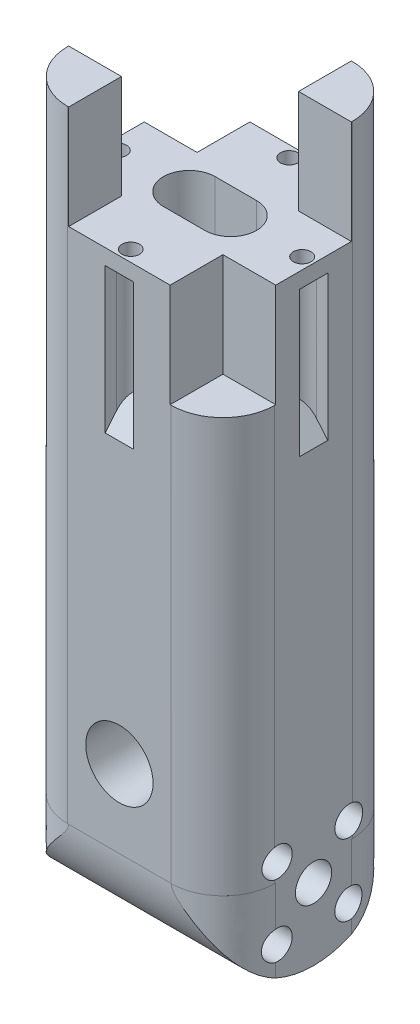
SolidWorks part; units mm, degrees
ref_plane "Plan de face" through (0, 0, 0) normal (0, 0, 1) x (1, 0, 0)
ref_plane "Plan de dessus" through (0, 0, 0) normal (0, 1, 0) x (1, 0, 0)
ref_plane "Plan de droite" through (0, 0, 0) normal (1, 0, 0) x (0, 0, -1)
sketch "Esquisse3" plane through (0, 0, 0) normal (0, 1, 0) x (1, 0, 0)
  line L1 (-20, -17.5) -> (20, -17.5)
  line L2 (-20, -17.5) -> (-20, 17.5)
  line L3 (-20, 17.5) -> (20, 17.5)
  line L4 (20, -17.5) -> (20, 17.5)
  line L5 (-20, -17.5) -> (20, 17.5) construction
  line L6 (-20, 17.5) -> (20, -17.5) construction
  point P0 (0, 0)
  dimension "D1" = 40
  dimension "D2" = 35
extrude "Boss.-Extru.2" add sketch "Esquisse3" along normal blind 120
fillet "Congé1" radius 10 4 edges at (-20, 60, -17.5) (-20, 60, 17.5) (20, 60, -17.5) (20, 60, 17.5)
sketch "Esquisse4" plane through (0, 120, 0) normal (0, 1, 0) x (1, 0, 0)
  line L10 (-20, 17.5) -> (9.8, 17.5)
  line L11 (9.8, 17.5) -> (9.8, 7.3)
  line L12 (9.8, 7.3) -> (20, 7.3)
  line L13 (20, 7.3) -> (20, -17.5)
  line L14 (20, -17.5) -> (-9.8, -17.5)
  line L15 (-9.8, -17.5) -> (-9.8, -7.3)
  line L16 (-9.8, -7.3) -> (-20, -7.3)
  line L17 (-20, -7.3) -> (-20, 17.5)
  line L19 (20, -7.5) -> (20, 7.5) construction
  line L20 (10, 17.5) -> (-10, 17.5) construction
  line L21 (-20, 7.5) -> (-20, -7.5) construction
  line L22 (-10, -17.5) -> (10, -17.5) construction
  arc A0 (-20, -7.5) -> (-10, -17.5) centre (-10, -7.5) ccw construction
  arc A1 (20, 7.5) -> (10, 17.5) centre (10, 7.5) ccw construction
  dimension "D4" = 0.2
  dimension "D1" = 0.2
  dimension "D2" = 0.2
  dimension "D3" = 0.2
extrude "Enlèv. mat.-Extru.1" cut sketch "Esquisse4" against normal blind 20
sketch "Esquisse5" plane through (0, 100, 0) normal (0, 1, 0) x (1, 0, 0)
  line L0 (-20, 7.5) -> (-20, -7.3) construction
  line L9 (-20, 17.5) -> (-9.8, 17.5)
  line L10 (-20, 17.5) -> (-20, 7.3)
  line L11 (-20, 7.3) -> (-9.8, 7.3)
  line L12 (-9.8, 17.5) -> (-9.8, 7.3)
  line L13 (20, -17.5) -> (9.8, -17.5)
  line L14 (20, -17.5) -> (20, -7.3)
  line L15 (20, -7.3) -> (9.8, -7.3)
  line L16 (9.8, -17.5) -> (9.8, -7.3)
  line L17 (9.8, 17.5) -> (-10, 17.5) construction
  line L18 (20, -7.5) -> (20, 7.3) construction
  line L19 (-9.8, -17.5) -> (10, -17.5) construction
  arc A0 (-10, 17.5) -> (-20, 7.5) centre (-10, 7.5) ccw construction
  arc A1 (10, -17.5) -> (20, -7.5) centre (10, -7.5) ccw construction
  dimension "D2" = 0.2
  dimension "D1" = 0.2
  dimension "D3" = 0.2
  dimension "D4" = 0.2
extrude "Enlèv. mat.-Extru.2" cut sketch "Esquisse5" against normal blind 20
sketch "Esquisse6" plane through (0, 100, 0) normal (0, 1, 0) x (1, 0, 0)
  line L0 (-4, 0) -> (4, 0) construction
  line L1 (-4, 5) -> (4, 5)
  line L2 (-4, -5) -> (4, -5)
  arc A0 (-4, 5) -> (-4, -5) centre (-4, 0) ccw
  arc A1 (4, -5) -> (4, 5) centre (4, 0) ccw
  point P2 (0, 0)
  dimension "D2" = 5
  dimension "D1" = 8
extrude "Enlèv. mat.-Extru.3" cut sketch "Esquisse6" against normal blind 90
sketch "Esquisse8" plane through (-20, 0, 0) normal (-1, 0, 0) x (0, 0, 1)
  line L0 (-7.5, 0) -> (7.5, 0) construction
  line L1 (17.5, 120) -> (17.5, 0) construction
  line L2 (-17.5, 0) -> (17.5, 0)
  arc A0 (-17.5, 0) -> (17.5, 0) centre (0, 0) ccw
extrude "Boss.-Extru.3" add sketch "Esquisse8" against normal blind 40
sketch "Esquisse10" plane through (0, 0, 0) normal (0, 1, 0) x (1, 0, 0)
  line L0 (-2.75, 0) -> (2.75, 0) construction
  line L1 (-10.75, -11) -> (-2.75, -11)
  line L2 (-10.75, -11) -> (-10.75, 11)
  line L3 (-10.75, 11) -> (-2.75, 11)
  line L4 (-2.75, -11) -> (-2.75, 11)
  line L5 (2.75, -11) -> (10.75, -11)
  line L6 (2.75, -11) -> (2.75, 11)
  line L7 (2.75, 11) -> (10.75, 11)
  line L8 (10.75, -11) -> (10.75, 11)
  point P8 (-2.75, 0)
  point P10 (2.75, 0)
  point P14 (0, 0)
  dimension "D1" = 8
  dimension "D2" = 2.75
  dimension "D3" = 22
extrude "Enlèv. mat.-Extru.5" cut sketch "Esquisse10" against normal through all and the other way blind 7.5
sketch "Esquisse12" plane through (2.75, 0, 0) normal (1, 0, 0) x (0, 0, -1)
  line L0 (-11, -13.6107) -> (11, -13.6107) construction
  line L1 (6.5, -40.4793) -> (-6.5, -40.4793)
  line L2 (6.5, -40.4793) -> (6.5, 5.4793)
  line L3 (6.5, 5.4793) -> (-6.5, 5.4793)
  line L4 (-6.5, -40.4793) -> (-6.5, 5.4793)
  line L5 (6.5, -40.4793) -> (-6.5, 5.4793) construction
  line L6 (6.5, 5.4793) -> (-6.5, -40.4793) construction
  arc A0 (-11, -13.6107) -> (11, -13.6107) centre (0, 0) ccw construction
  point P0 (0, -17.5)
  dimension "D1" = 13
  dimension "D2" = 19.09
extrude "Enlèv. mat.-Extru.7" cut sketch "Esquisse12" against normal blind 6
hole_wizard "Ø1.0mm Dowel Hole1" positions "Esquisse13" profile "Esquisse14" hole size "Ø1.0" standard "ANSI Metric" end condition through all
sketch "Esquisse13" plane through (20, 0, 0) normal (1, 0, 0) x (0, 0, -1)
  arc A1 (-17.5, 0) -> (17.5, 0) centre (0, 0) ccw construction
  point P0 (0, -3.6)
  point P10 (0, -17.5)
  dimension "D1" = 13.9
sketch "Esquisse14" plane through (20, -3.6, 0) normal (0, 1, 0) x (0, 0, -1)
  line L0 (0, 0) -> (0, 40)
  line L1 (0, 40) -> (3.5, 40)
  line L2 (3.5, 40) -> (3.5, 0)
  line L5 (3.5, 0) -> (0, 0)
  line L11 (0, -6.35) -> (0, 107.95) construction
  dimension "Diamètre du perçage jusqu'au prochain" = 7
  dimension "Profondeur du perçage jusqu'au prochain" = 40
hole_wizard "M5 Clearance Hole2" positions "Esquisse19" profile "Esquisse20" hole size "M5" standard "ANSI Metric" end condition through all
sketch "Esquisse19" plane through (20, 0, 0) normal (1, 0, 0) x (0, 0, -1)
  circle A0 centre (0, -3.6) radius 3.5 construction
  point P0 (-6.915, -10.515)
  point P2 (6.915, -10.515)
  point P4 (6.915, 3.315)
  point P6 (-6.915, 3.315)
  dimension "D4" = 6.915
  dimension "D1" = 13.83
  dimension "D2" = 13.83
  dimension "D3" = 6.915
sketch "Esquisse20" plane through (20, -10.515, 6.915) normal (0, 1, 0) x (0, 0, -1)
  line L0 (0, 0) -> (0, 40)
  line L1 (0, 40) -> (2.8, 40)
  line L2 (2.8, 40) -> (2.8, 0)
  line L5 (2.8, 0) -> (0, 0)
  line L11 (0, -6.35) -> (0, 107.95) construction
  dimension "Diamètre du perçage jusqu'au prochain" = 5.6
  dimension "Profondeur du perçage jusqu'au prochain" = 40
sketch "Esquisse21" plane through (0, 100, 0) normal (0, 1, 0) x (1, 0, 0)
  line L0 (-9.8, -17.5) -> (9.8, -17.5) construction
  line L1 (-20, 7.3) -> (-20, -7.3) construction
  circle A0 centre (0, -15.3) radius 1.7
  circle A1 centre (-17.8, 0) radius 1.7
  dimension "D1" = 3.4
  dimension "D2" = 2.2
  dimension "D3" = 2.2
extrude "Enlèv. mat.-Extru.8" cut sketch "Esquisse21" against normal blind 3
sketch "Esquisse22" plane through (0, 97, 0) normal (0, 1, 0) x (1, 0, 0)
  circle A0 centre (-17.8, 0) radius 2.75
  dimension "D1" = 5.5
extrude "Enlèv. mat.-Extru.9" cut sketch "Esquisse22" against normal blind 20
sketch "Esquisse23" plane through (0, 97, 0) normal (0, 1, 0) x (1, 0, 0)
  circle A0 centre (0, -15.3) radius 2.75
  dimension "D1" = 5.5
extrude "Enlèv. mat.-Extru.10" cut sketch "Esquisse23" against normal blind 20
sketch "Esquisse24" plane through (-20, 0, 0) normal (-1, 0, 0) x (0, 0, 1)
  line L0 (-1.65, 97) -> (1.65, 97) construction
  line L1 (2.75, 97) -> (-2.75, 97)
  line L2 (2.75, 97) -> (2.75, 77)
  line L3 (2.75, 77) -> (-2.75, 77)
  line L4 (-2.75, 97) -> (-2.75, 77)
  line L5 (2.75, 97) -> (-2.75, 77) construction
  line L6 (2.75, 77) -> (-2.75, 97) construction
  line L7 (-1.65, 77) -> (1.65, 77) construction
  point P0 (0, 87)
  dimension "D1" = 5.5
extrude "Enlèv. mat.-Extru.11" cut sketch "Esquisse24" against normal blind 2.2
sketch "Esquisse25" plane through (0, 0, 17.5) normal (0, 0, 1) x (1, 0, 0)
  line L1 (2.75, 97) -> (-2.75, 97)
  line L2 (2.75, 97) -> (2.75, 77)
  line L3 (2.75, 77) -> (-2.75, 77)
  line L4 (-2.75, 97) -> (-2.75, 77)
  line L5 (2.75, 97) -> (-2.75, 77) construction
  line L6 (2.75, 77) -> (-2.75, 97) construction
  line L7 (-1.65, 97) -> (1.65, 97) construction
  line L8 (-1.65, 77) -> (1.65, 77) construction
  point P0 (0, 87)
  dimension "D1" = 5.5
extrude "Enlèv. mat.-Extru.12" cut sketch "Esquisse25" against normal blind 2.2
mirror "Symétrie2" about plane through (0, 0, 0) normal (1, 0, 0) of "Enlèv. mat.-Extru.11", "Enlèv. mat.-Extru.9", "Enlèv. mat.-Extru.8"
mirror "Symétrie3" about plane through (0, 0, 0) normal (0, 0, 1) of "Enlèv. mat.-Extru.12", "Enlèv. mat.-Extru.10", "Enlèv. mat.-Extru.8"
chamfer "Chanfrein1" distance 8 angle 40 4 edges at (-20, 77, 0) (0, 77, 17.5) (20, 77, 0) (0, 77, -17.5) first distance on face at (-20, 42.5543, 0) first distance on face at (0, 75, 17.5) first distance on face at (20, 42.5543, 0) first distance on face at (0, 75, -17.5)
sketch "Esquisse26" plane through (0, 0, 0) normal (0, 1, 0) x (1, 0, 0)
  line L0 (-9.8, 17.5) -> (-20, 17.5)
  line L2 (9.8, 17.5) -> (20, 17.5)
  line L3 (20, 17.5) -> (20, 7.3)
  line L5 (-9.8, -17.5) -> (-20, -17.5)
  line L6 (-20, -17.5) -> (-20, -7.3)
  line L7 (20, -7.3) -> (20, -17.5)
  line L9 (-20, 17.5) -> (-20, 7.5)
  line L10 (20, -17.5) -> (10, -17.5)
  arc A1 (20, 7.5) -> (10, 17.5) centre (10, 7.5) ccw construction
  arc A2 (-20, -7.5) -> (-10, -17.5) centre (-10, -7.5) ccw construction
  arc A4 (-10, 17.5) -> (-20, 7.5) centre (-10, 7.5) ccw construction
  arc A5 (10, -17.5) -> (20, -7.5) centre (10, -7.5) ccw construction
  spline S0 degree 2 poles (-20, 7.5) (-19.1208, 16.7623) (-9.8, 17.5) knots 0 0 0 1 1 1
  spline S1 degree 2 poles (9.8, 17.5) (19.2421, 16.7421) (20, 7.3) knots 0 0 0 1 1 1
  spline S2 degree 2 poles (-20, -7.3) (-19.2421, -16.7421) (-9.8, -17.5) knots 0 0 0 1 1 1
  spline S3 degree 2 poles (10, -17.5) (19.2623, -16.6208) (20, -7.3) knots 0 0 0 1 1 1
extrude "Enlèv. mat.-Extru.13" cut sketch "Esquisse26" against normal through all
sketch "Esquisse27" plane through (0, 0, 17.5) normal (0, 0, 1) x (1, 0, 0)
  line L0 (-9.8, 100) -> (9.8, 100) construction
  line L1 (20, 80) -> (20, 6.0532) construction
  circle A0 centre (0, 15) radius 6.5
  dimension "D2" = 13
  dimension "D1" = 85
  dimension "D3" = 20
extrude "Enlèv. mat.-Extru.14" cut sketch "Esquisse27" against normal through all
